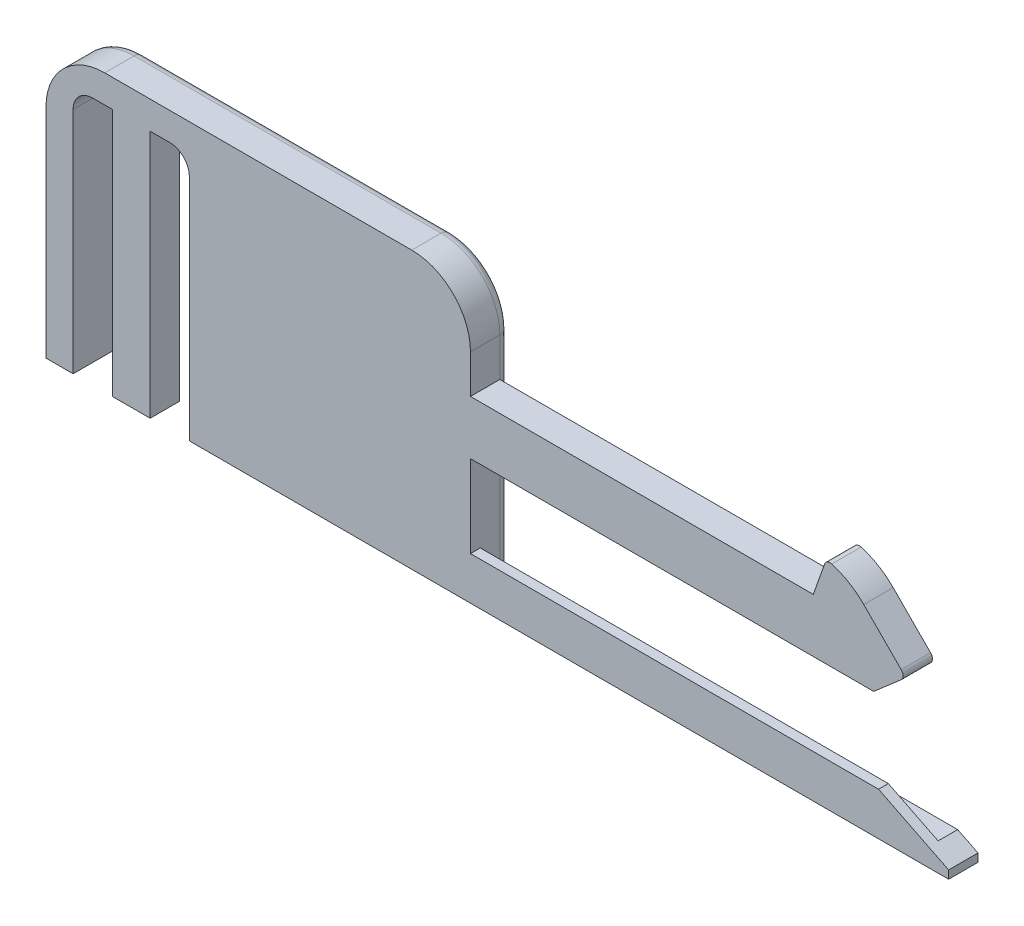
SolidWorks part; units mm, degrees
note: The reader was unsure of these and kept them because the rebuilt part matched: shared geometry of "Sketch1<3>", "Sketch1<4>", "Sketch1<5>".
ref_plane "Front Plane" through (0, 0, 0) normal (0, 0, 1) x (1, 0, 0)
ref_plane "Top Plane" through (0, 0, 0) normal (0, 1, 0) x (1, 0, 0)
ref_plane "Right Plane" through (0, 0, 0) normal (1, 0, 0) x (0, 0, -1)
other "Configuration Table"
sketch "Sketch1" plane through (0, 0, 0) normal (0, 0, 1) x (1, 0, 0)
  line L0 (0, 0) -> (89.0024, 0) construction
  line L1 (55.054, 28.2349) -> (55.054, -28.2349)
  line L2 (7.62, 35.8549) -> (47.434, 35.8549)
  line L3 (18.5886, 29.7055) -> (18.5886, -29.7055)
  line L4 (55.054, 23.2235) -> (99.5198, 23.2235)
  line L5 (99.5198, 23.2235) -> (100.9845, 27.3563)
  line L6 (0, 28.2349) -> (0, -28.2349)
  line L7 (55.054, 19.3248) -> (110.9117, 19.3248)
  line L8 (6.0585, 32.2455) -> (16.0486, 32.2455)
  line L9 (3.5185, 29.7055) -> (3.5185, -29.7055)
  line L10 (55.054, 2.3592) -> (114.4416, 2.3592)
  line L11 (114.4416, 2.3592) -> (117.0745, 1.049)
  line L12 (55.054, 5.5719) -> (107.9851, 5.5719)
  line L13 (107.9851, 5.5719) -> (114.4416, 2.3592)
  line L14 (106.0691, 25.3555) -> (110.9225, 20.4667)
  line L15 (107.3549, 16.2408) -> (110.9117, 19.3248)
  line L16 (55.054, 16.2408) -> (107.3549, 16.2408)
  line L17 (55.054, -16.2408) -> (107.3549, -16.2408)
  line L18 (107.3549, -16.2408) -> (110.9117, -19.3248)
  line L19 (106.0691, -25.3555) -> (110.9225, -20.4667)
  line L20 (107.9851, -5.5719) -> (114.4416, -2.3592)
  line L21 (55.054, -5.5719) -> (107.9851, -5.5719)
  line L22 (114.4416, -2.3592) -> (117.0745, -1.049)
  line L23 (55.054, -2.3592) -> (114.4416, -2.3592)
  line L24 (6.0585, -32.2455) -> (16.0486, -32.2455)
  line L25 (55.054, -19.3248) -> (110.9117, -19.3248)
  line L26 (99.5198, -23.2235) -> (101.2167, -28.0117)
  line L27 (55.054, -23.2235) -> (99.5198, -23.2235)
  line L28 (7.62, -35.8549) -> (47.434, -35.8549)
  line L29 (18.5886, 27.618) -> (41.8292, 27.618)
  line L30 (48.6376, 20.8097) -> (48.6376, -20.8097)
  line L31 (18.5886, -27.618) -> (41.8292, -27.618)
  line L32 (117.0745, 1.049) -> (117.0745, -1.049)
  line L33 (8.5985, 32.2455) -> (8.5985, -32.2455)
  line L34 (13.5086, 32.2455) -> (13.5086, -32.2455)
  arc A0 (101.9185, 27.8326) -> (106.0691, 25.3555) centre (99.1624, 18.4988) cw
  arc A1 (110.9225, 20.4667) -> (110.9117, 19.3248) centre (110.4125, 19.9005) cw
  arc A2 (47.434, 35.8549) -> (55.054, 28.2349) centre (47.434, 28.2349) cw
  arc A3 (6.0585, 32.2455) -> (3.5185, 29.7055) centre (6.0585, 29.7055) ccw
  arc A4 (16.0486, 32.2455) -> (18.5886, 29.7055) centre (16.0486, 29.7055) cw
  arc A5 (0, 28.2349) -> (7.62, 35.8549) centre (7.62, 28.2349) cw
  arc A6 (0, -28.2349) -> (7.62, -35.8549) centre (7.62, -28.2349) ccw
  arc A7 (16.0486, -32.2455) -> (18.5886, -29.7055) centre (16.0486, -29.7055) ccw
  arc A8 (6.0585, -32.2455) -> (3.5185, -29.7055) centre (6.0585, -29.7055) cw
  arc A9 (47.434, -35.8549) -> (55.054, -28.2349) centre (47.434, -28.2349) ccw
  arc A10 (110.9225, -20.4667) -> (110.9117, -19.3248) centre (110.4125, -19.9005) ccw
  arc A11 (101.2167, -28.0117) -> (106.0691, -25.3555) centre (99.1624, -18.4988) ccw
  arc A12 (41.8292, 27.618) -> (48.6376, 20.8097) centre (41.8292, 20.8097) cw
  arc A13 (41.8292, -27.618) -> (48.6376, -20.8097) centre (41.8292, -20.8097) ccw
  arc A14 (100.9845, 27.3563) -> (101.9185, 27.8326) centre (101.7027, 27.1018) cw
  point P11 (55.054, 0)
  point P19 (48.387, 35.3698)
  point P53 (48.387, -35.3698)
  point P60 (3.5185, 0)
  point P63 (18.5886, 0)
  point P72 (48.6376, 0)
  point P79 (101.2167, 28.0117)
  dimension "D1" = 0.762
  dimension "D2" = 7.62
  dimension "D3" = 2.54
  dimension "D4" = 7.62
  dimension "D5" = 5.08
  dimension "D6" = 5.08
  dimension "D7" = 5.08
extrude "Extrude1" add sketch "Sketch1" along normal mid plane 10.16
extrude "Extrude2" add sketch "Sketch1<3>" along normal mid plane 2.54 contours L16 L15 L7 L1 | L20 L23 L1 L21 | L10 L13 L12 L1 | L25 L18 L17 L1
sketch "Sketch1<3>" plane through (0, 0, 0) normal (0, 0, 1) x (1, 0, 0) same geometry as "Sketch1"
extrude "Extrude3" add sketch "Sketch1<4>" along normal mid plane 7.62
sketch "Sketch1<4>" plane through (0, 0, 0) normal (0, 0, 1) x (1, 0, 0) same geometry as "Sketch1"
extrude "Extrude4" add sketch "Sketch1<5>" along normal mid plane 7.62 contours L0 L3 L31 A13 L30 | L3 L0 L30 A12 L29 | L0 L33 L24 L34 | L33 L0 L34 L8
sketch "Sketch1<5>" plane through (0, 0, 0) normal (0, 0, 1) x (1, 0, 0) same geometry as "Sketch1"
fillet "Fillet2" radius 1.27 10 edges at (30.2089, -27.618, -3.81) (30.2089, -27.618, 3.81) (46.6434, -25.6239, -3.81) (46.6434, -25.6239, 3.81) (48.6376, 0, -3.81) (48.6376, 0, 3.81) (46.6434, 25.6239, -3.81) (46.6434, 25.6239, 3.81) (30.2089, 27.618, -3.81) (30.2089, 27.618, 3.81)
fillet "Fillet3" radius 1.27 16 edges at (2.2318, 33.6231, -5.08) (2.2318, 33.6231, 5.08) (0, 0, -5.08) (0, 0, 5.08) (2.2318, -33.6231, -5.08) (2.2318, -33.6231, 5.08) (27.527, -35.8549, -5.08) (27.527, -35.8549, 5.08) (52.8221, -33.6231, -5.08) (52.8221, -33.6231, 5.08) (55.054, 0, -5.08) (55.054, 0, 5.08) (52.8221, 33.6231, -5.08) (52.8221, 33.6231, 5.08) (27.527, 35.8549, -5.08) (27.527, 35.8549, 5.08)
sketch "Sketch2" plane through (117.0745, 0, 0) normal (1, 0, 0) x (0, 0, -1)
  line L0 (0, 0) -> (0, 35.8549)
  line L1 (-3.81, 35.8549) -> (3.81, 35.8549) construction
  line L2 (0, 0) -> (5.08, 0)
  line L3 (5.08, 28.2349) -> (5.08, -28.2349) construction
extrude "Cut-Extrude1" cut sketch "Sketch2" against normal through all and the other way through all flip side to cut
